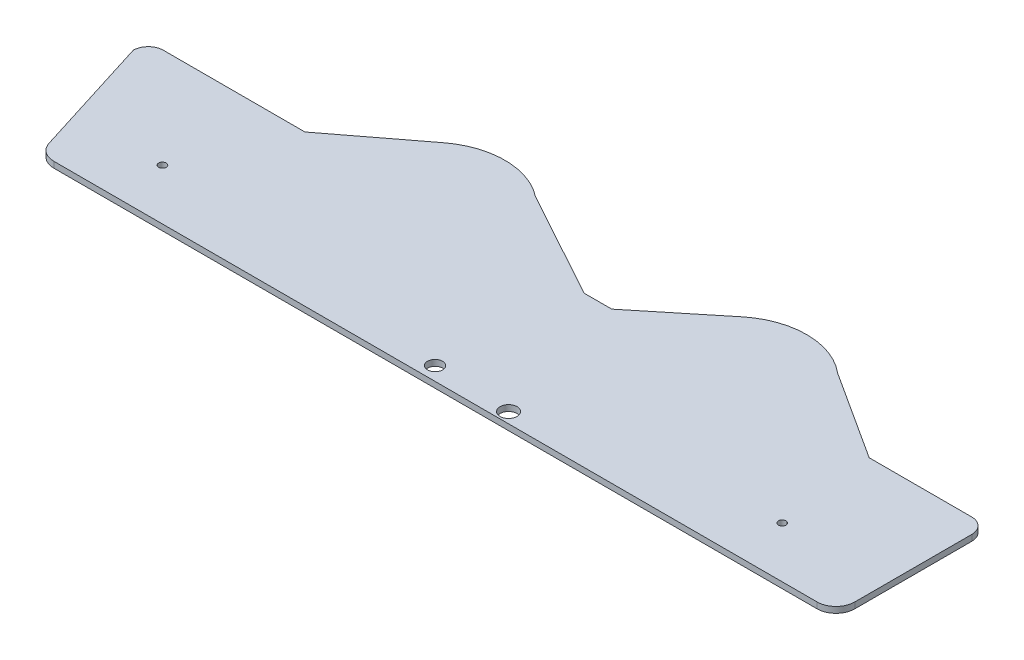
SolidWorks part; units mm, degrees
ref_plane "Front" through (0, 0, 0) normal (0, 0, 1) x (1, 0, 0)
ref_plane "Top" through (0, 0, 0) normal (0, 1, 0) x (1, 0, 0)
ref_plane "Right" through (0, 0, 0) normal (1, 0, 0) x (0, 0, -1)
sketch "Sketch1" plane through (0, 0, 0) normal (0, 1, 0) x (1, 0, 0)
  line L0 (0, 142) -> (42, 8)
  line L1 (0, 0) -> (444.5, 0)
  line L2 (0, 0) -> (0, 150)
  line L3 (0, 150) -> (444.5, 150)
  line L4 (444.5, 0) -> (444.5, 150)
  circle A0 centre (8, 142) radius 8
  circle A1 centre (50, 8) radius 8
  circle A2 centre (436.5, 142) radius 8
  circle A3 centre (436.5, 8) radius 8
  circle A4 centre (265.3381, 75.6339) radius 4.5112
  circle A5 centre (146.2694, 139.8404) radius 3.7162
  circle A6 centre (307.6065, 140.7106) radius 4.3136
  dimension "D3" = 8
  dimension "D5" = 8
  dimension "D7" = 8
  dimension "D9" = 8
  dimension "D1" = 150
  dimension "D2" = 444.5
  dimension "D4" = 8
  dimension "D6" = 50
  dimension "D8" = 8
  dimension "D10" = 8
extrude "Boss-Extrude1" add sketch "Sketch1" along normal blind 3.175 contours A3 L4 A2 L3 A0 L0 A1 L1 | A1 | A0 L0 | A2 | A3 region at (8.0436, 0, -142.0137) region at (232.4883, 0, -76.2813) region at (50, 0, -8) region at (436.5, 0, -142) region at (436.5, 0, -8)
sketch "Sketch2" plane through (0, 0, 0) normal (0, 0, 1) x (1, 0, 0)
  line L1 (-78.5546, 38.0306) -> (518.9117, 38.0306)
  line L2 (-78.5546, 38.0306) -> (-78.5546, -22.9419)
  line L3 (-78.5546, -22.9419) -> (518.9117, -22.9419)
  line L4 (518.9117, 38.0306) -> (518.9117, -22.9419)
extrude "Cut-Extrude1" cut sketch "Sketch2" against normal blind 70
fillet "Fillet1" radius 10 1 edges at (22.5672, 1.5875, -70)
fillet "Fillet2" radius 10 1 edges at (444.5, 1.5875, -70)
sketch "Sketch3" plane through (0, 3.175, 0) normal (0, 1, 0) x (1, 0, 0)
  line L0 (444.5, 80) -> (444.5, 142) construction
  line L1 (29.9125, 70) -> (434.5, 70) construction
  circle A0 centre (224.75, 77.255) radius 3.9908
  dimension "D1" = 219.75
  dimension "D2" = 7.255
extrude "Cut-Extrude2" cut sketch "Sketch3" against normal blind 10
sketch "Sketch4" plane through (0, 3.175, 0) normal (0, 1, 0) x (1, 0, 0)
  line L0 (29.9125, 70) -> (434.5, 70) construction
  line L1 (444.5, 80) -> (444.5, 142) construction
  circle A0 centre (60.5, 97) radius 2
  dimension "D3" = 4
  dimension "D1" = 27
  dimension "D2" = 384
extrude "Cut-Extrude3" cut sketch "Sketch4" against normal through all
sketch "Sketch5" plane through (0, 3.175, 0) normal (0, 1, 0) x (1, 0, 0)
  line L0 (444.5, 80) -> (444.5, 142) construction
  line L1 (29.9125, 70) -> (434.5, 70) construction
  circle A0 centre (389, 97) radius 2
  dimension "D1" = 55.5
  dimension "D3" = 4
  dimension "D2" = 27
extrude "Cut-Extrude4" cut sketch "Sketch5" against normal blind 10
sketch "Sketch6" plane through (0, 0, 0) normal (0, 1, 0) x (1, 0, 0)
  circle A0 centre (149, 150.0404) radius 40
  dimension "D1" = 80
  dimension "D2" = 141
extrude "Boss-Extrude2" add sketch "Sketch6" along normal blind 3.175
sketch "Sketch7" plane through (0, 0, 0) normal (0, 1, 0) x (1, 0, 0)
  line L0 (124.1645, 181.3964) -> (82.7029, 149.7505)
  line L1 (173.8355, 181.3964) -> (231.4689, 149.7505)
  line L2 (82.7029, 149.7505) -> (231.4689, 149.7505)
  line L3 (124.1645, 181.3964) -> (173.8355, 181.3964)
  arc A0 (189, 150) -> (109, 150) centre (149, 150.0404) ccw construction
extrude "Boss-Extrude3" add sketch "Sketch7" along normal blind 3.175
sketch "Sketch9" plane through (0, 0, 0) normal (0, 1, 0) x (1, 0, 0)
  line L0 (444.5, 80) -> (444.5, 142) construction
  line L1 (231.0146, 150) -> (436.5, 150) construction
  line L2 (283.7342, 181.0103) -> (245.6734, 150)
  line L3 (245.6734, 150) -> (269, 150)
  line L4 (334.2658, 181.0103) -> (397.5744, 150)
  circle A0 centre (309, 150) radius 40
  dimension "D1" = 135.5
  dimension "D2" = 0
extrude "Boss-Extrude4" add sketch "Sketch9" along normal blind 3.175 contours A0 L2 L3 | A0 region at (263.2337, 0, -158.4181) region at (309, 0, -150)
sketch "Sketch12" plane through (0, 0, 0) normal (0, 1, 0) x (1, 0, 0)
  line L0 (326.1663, 186.1292) -> (382.1065, 150)
  line L1 (349, 150) -> (436.5, 150) construction
  line L2 (382.1065, 150) -> (340.3988, 150)
  line L3 (340.3988, 150) -> (326.1663, 186.1292)
  arc A0 (349, 150) -> (283.7342, 181.0103) centre (309, 150) ccw construction
extrude "Boss-Extrude6" add sketch "Sketch12" along normal blind 3.175
sketch "Sketch14" plane through (0, 3.175, 0) normal (0, 1, 0) x (1, 0, 0)
  circle A0 centre (140, 139.2404) radius 6.619
  arc A1 (8, 150) -> (0, 142) centre (8, 142) ccw construction
  arc A2 (173.8355, 181.3964) -> (124.1645, 181.3964) centre (149, 150.0404) ccw construction
  point P8 (149, 190.0404)
  dimension "D2" = 50.8
  dimension "D1" = 132
